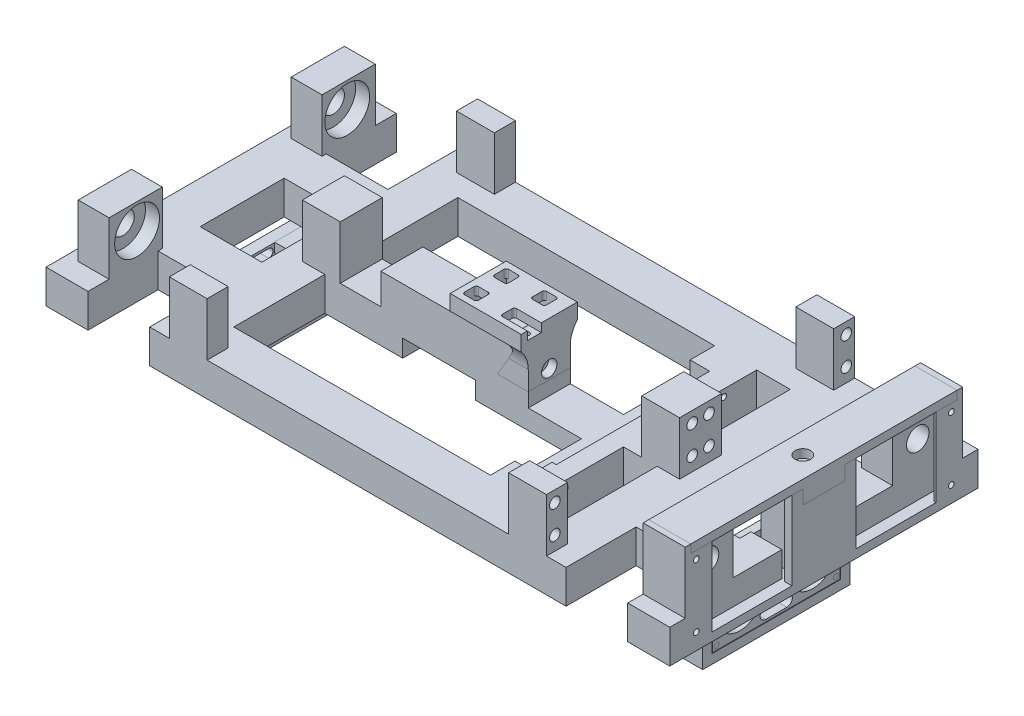
SolidWorks part; units mm, degrees
other "DogBody"
other "EspHolder"
other "HCSR04 Holder Front"
other "DisplayCover"
other "pin lu"
other "pin ru"
other "pin rd"
other "frontCover"
other "HCSR04 Holder Back"
other "pin rd2"
other "pin ru2"
other "pin lu2"
other "pin ld2"
other "frontCover2"
other "pin ld"
ref_plane "Front Plane" through (0, 0, 0) normal (0, 0, 1) x (1, 0, 0)
ref_plane "Top Plane" through (0, 0, 0) normal (0, 1, 0) x (1, 0, 0)
ref_plane "Right Plane" through (0, 0, 0) normal (1, 0, 0) x (0, 0, -1)
sketch "Sketch1" plane through (0, 0, 0) normal (0, 1, 0) x (1, 0, 0)
  line L0 (-96.3, -55) -> (-96.3, -7.5)
  line L1 (-111.3, -55) -> (-96.3, -55)
  line L2 (-111.3, -55) -> (-111.3, 55)
  line L3 (-111.3, 55) -> (-96.3, 55)
  line L4 (111.3, -55) -> (111.3, 55)
  line L5 (96.3, 55) -> (96.3, 7.5)
  line L6 (-74.3, -55) -> (-74.3, -7.5)
  line L7 (-59.3, -40) -> (-59.3, -7.5)
  line L8 (74.3, -55) -> (74.3, -7.5)
  line L9 (59.3, -40) -> (59.3, -7.5)
  line L10 (-111.3, 0) -> (111.3, 0) construction
  line L11 (-96.3, -7.5) -> (-74.3, -7.5)
  line L12 (-96.3, 7.5) -> (-74.3, 7.5)
  line L15 (-59.3, 40) -> (59.3, 40)
  line L16 (-74.3, 55) -> (74.3, 55)
  line L18 (96.3, 55) -> (111.3, 55)
  line L19 (96.3, -55) -> (111.3, -55)
  line L21 (-74.3, -55) -> (74.3, -55)
  line L22 (-59.3, -40) -> (59.3, -40)
  line L23 (-96.3, 7.5) -> (-96.3, 55)
  line L24 (-74.3, 7.5) -> (-74.3, 55)
  line L25 (-59.3, 7.5) -> (-59.3, 40)
  line L26 (59.3, 7.5) -> (59.3, 40)
  line L27 (74.3, 7.5) -> (74.3, 55)
  line L28 (96.3, -7.5) -> (96.3, -55)
  line L29 (-111.3, 7.5) -> (111.3, 7.5) construction
  line L30 (-111.3, -7.5) -> (111.3, -7.5) construction
  line L31 (74.3, -7.5) -> (96.3, -7.5)
  line L32 (74.3, 7.5) -> (96.3, 7.5)
  line L33 (-59.3, -7.5) -> (59.3, -7.5)
  line L34 (-59.3, 7.5) -> (59.3, 7.5)
  line L35 (-96.3, 55) -> (-74.3, 55) construction
  line L36 (74.3, 55) -> (96.3, 55) construction
  line L37 (74.3, -55) -> (96.3, -55) construction
  line L38 (-74.3, -55) -> (-96.3, -55) construction
  dimension "D1" = 55
  dimension "D2" = 110
  dimension "D3" = 15
  dimension "D4" = 22
  dimension "D5" = 15
  dimension "D6" = 15
  dimension "D7" = 22
  dimension "D8" = 15
  dimension "D11" = 80
  dimension "D12" = 40
  dimension "D13" = 222.6
  dimension "D14" = 111.3
  dimension "D9" = 7.5
  dimension "D10" = 7.5
extrude "Boss-Extrude1" add sketch "Sketch1" along normal blind 12
sketch "Sketch2" plane through (0, 12, 0) normal (0, 1, 0) x (1, 0, 0)
  line L0 (-74.3, 55) -> (-74.3, 7.5) construction
  line L1 (-67.3, 47.5) -> (-55.3, 47.5)
  line L2 (-67.3, 47.5) -> (-67.3, 55)
  line L3 (-67.3, 55) -> (-55.3, 55)
  line L4 (-55.3, 47.5) -> (-55.3, 55)
  line L5 (74.3, 55) -> (-74.3, 55) construction
  line L6 (-67.3, 52) -> (-55.3, 52) construction
  line L7 (-112.3144, 27.5) -> (114.0355, 27.5) construction
  line L8 (0, 0) -> (0, 64.2149) construction
  line L9 (-67.3, 3) -> (-55.3, 3) construction
  line L12 (-67.3, 7.5) -> (-55.3, 7.5)
  line L14 (0, 0) -> (-136.6898, 0) construction
  line L15 (-67.3, -52) -> (-55.3, -52) construction
  line L16 (-67.3, -55) -> (-55.3, -55)
  line L17 (-55.3, -47.5) -> (-55.3, -55)
  line L18 (-67.3, -47.5) -> (-55.3, -47.5)
  line L19 (-67.3, -47.5) -> (-67.3, -55)
  line L20 (-67.3, -3) -> (-55.3, -3) construction
  line L21 (-67.3, -7.5) -> (-55.3, -7.5)
  line L22 (-55.3, -7.5) -> (-55.3, 0)
  line L23 (-55.3, 0) -> (-55.3, 7.5)
  line L24 (-67.3, 7.5) -> (-67.3, 0)
  line L25 (-67.3, 0) -> (-67.3, -7.5)
  line L26 (67.3, -52) -> (55.3, -52) construction
  line L27 (67.3, -47.5) -> (67.3, -55)
  line L28 (67.3, -47.5) -> (55.3, -47.5)
  line L29 (55.3, -47.5) -> (55.3, -55)
  line L30 (67.3, -55) -> (55.3, -55)
  line L31 (67.3, -3) -> (55.3, -3) construction
  line L32 (67.3, 3) -> (55.3, 3) construction
  line L33 (67.3, 7.5) -> (67.3, 0)
  line L34 (67.3, 7.5) -> (55.3, 7.5)
  line L35 (55.3, 0) -> (55.3, 7.5)
  line L36 (55.3, -7.5) -> (55.3, 0)
  line L37 (67.3, -7.5) -> (55.3, -7.5)
  line L38 (67.3, 0) -> (67.3, -7.5)
  line L39 (67.3, 52) -> (55.3, 52) construction
  line L40 (67.3, 55) -> (55.3, 55)
  line L41 (55.3, 47.5) -> (55.3, 55)
  line L42 (67.3, 47.5) -> (55.3, 47.5)
  line L43 (67.3, 47.5) -> (67.3, 55)
  point P29 (-55.3, 0)
  point P32 (-67.3, 0)
  dimension "D1" = 7
  dimension "D2" = 7.5
  dimension "D3" = 12
  dimension "D5" = 24.5
extrude "Boss-Extrude2" add sketch "Sketch2" along normal blind 19
sketch "Sketch3" plane through (-67.3, 0, 0) normal (-1, 0, 0) x (0, 0, 1)
  line L0 (-27.5, -10.7851) -> (-27.5, 36.9377) construction
  line L1 (-47.5, 31) -> (-47.5, 12) construction
  line L2 (-55, 12) -> (55, 12) construction
  line L3 (0, 0) -> (0, 40.8102) construction
  line L4 (-55, 0) -> (55, 0) construction
  circle A0 centre (-52, 17) radius 1.9
  circle A1 centre (-52, 27) radius 1.9
  circle A2 centre (-3, 17) radius 1.9
  circle A3 centre (-3, 27) radius 1.9
  circle A4 centre (3, 27) radius 1.9
  circle A5 centre (3, 17) radius 1.9
  circle A6 centre (52, 17) radius 1.9
  circle A7 centre (52, 27) radius 1.9
  dimension "D3" = 3.8
  dimension "D4" = 3.8
  dimension "D1" = 4.5
  dimension "D2" = 4.5
  dimension "D5" = 10
  dimension "D6" = 5
  dimension "D7" = 24.5
extrude "Cut-Extrude1" cut sketch "Sketch3" against normal through all
sketch "Sketch4" plane through (96.3, 0, 0) normal (-1, 0, 0) x (0, 0, 1)
  line L0 (47.5, 31) -> (47.5, 12) construction
  line L1 (-55, 12) -> (55, 12) construction
  line L2 (-1000, 0) -> (49000, 0) construction
  line L3 (0, -1000) -> (0, 49000) construction
  line L5 (-47.5, 12) -> (-28.5, 12)
  line L6 (-47.5, 12) -> (-47.5, 31)
  line L7 (-47.5, 31) -> (-28.5, 31)
  line L8 (-28.5, 12) -> (-28.5, 31)
  line L9 (47.5, 12) -> (28.5, 12)
  line L10 (47.5, 12) -> (47.5, 31)
  line L11 (47.5, 31) -> (28.5, 31)
  line L12 (28.5, 12) -> (28.5, 31)
  circle A0 centre (37.5, 22) radius 8
  circle A1 centre (-37.5, 22) radius 8
  dimension "D1" = 16
  dimension "D2" = 10
  dimension "D3" = 10
  dimension "D4" = 19
  dimension "D5" = 19
  dimension "D6" = 19
  dimension "D7" = 19
extrude "Boss-Extrude3" add sketch "Sketch4" against normal blind 5 separate body
sketch "Sketch6" plane through (101.3, 0, 0) normal (1, 0, 0) x (0, 0, -1)
  line L6 (-47.5, 12) -> (-28.5, 12)
  line L7 (-47.5, 12) -> (-47.5, 31)
  line L8 (-47.5, 31) -> (-28.5, 31)
  line L9 (-28.5, 12) -> (-28.5, 31)
  line L10 (47.5, 12) -> (28.5, 12)
  line L11 (47.5, 12) -> (47.5, 31)
  line L12 (47.5, 31) -> (28.5, 31)
  line L13 (28.5, 12) -> (28.5, 31)
  circle A0 centre (-37.5, 22) radius 4
  circle A1 centre (37.5, 22) radius 4
  dimension "D1" = 8
  dimension "D2" = 8
extrude "Boss-Extrude4" add sketch "Sketch6" along normal blind 6
mirror "Mirror1" about plane through (0, 0, 0) normal (1, 0, 0) of bodies 107 106
sketch "Sketch7" plane through (0, 0, 0) normal (0, 1, 0) x (1, 0, 0)
  line L0 (-96.3, 28.5) -> (-96.3, 47.5) construction
  line L1 (-96.3, 30) -> (-74.3, 30)
  line L2 (-96.3, 30) -> (-96.3, 15)
  line L4 (-74.3, 30) -> (-74.3, 15)
  line L5 (-67.3, 47.5) -> (-55.3, 47.5) construction
  line L7 (-96.3, 15) -> (-74.3, 15)
  line L9 (-1000, 0) -> (49000, 0) construction
  line L10 (0, -1000) -> (0, 49000) construction
  line L11 (96.3, 30) -> (96.3, 15)
  line L12 (96.3, 15) -> (74.3, 15)
  line L13 (74.3, 30) -> (74.3, 15)
  line L14 (96.3, 30) -> (74.3, 30)
  line L15 (96.3, -30) -> (74.3, -30)
  line L16 (74.3, -30) -> (74.3, -15)
  line L17 (96.3, -15) -> (74.3, -15)
  line L18 (96.3, -30) -> (96.3, -15)
  line L19 (-96.3, -30) -> (-96.3, -15)
  line L20 (-96.3, -15) -> (-74.3, -15)
  line L21 (-74.3, -30) -> (-74.3, -15)
  line L22 (-96.3, -30) -> (-74.3, -30)
  dimension "D1" = 17.5
  dimension "D2" = 15
  dimension "D3" = 22
extrude "Boss-Extrude5" add sketch "Sketch7" along normal blind 12
sketch "Sketch8" plane through (0, 12, 0) normal (0, 1, 0) x (1, 0, 0)
  line L1 (-96.3, 15) -> (-74.3, 15)
  line L2 (-96.3, 15) -> (-96.3, -15)
  line L3 (-96.3, -15) -> (-74.3, -15)
  line L4 (-74.3, 15) -> (-74.3, -15)
  line L5 (74.3, -15) -> (96.3, -15)
  line L6 (74.3, -15) -> (74.3, 15)
  line L7 (74.3, 15) -> (96.3, 15)
  line L8 (96.3, -15) -> (96.3, 15)
extrude "Cut-Extrude2" cut sketch "Sketch8" against normal through all
sketch "Sketch9" plane through (111.3, 0, 0) normal (1, 0, 0) x (0, 0, -1)
  line L1 (-47.5, 31) -> (-7.5, 31)
  line L2 (-47.5, 31) -> (-47.5, 3)
  line L3 (-47.5, 3) -> (-7.5, 3)
  line L4 (-7.5, 31) -> (-7.5, 3)
  line L5 (0, -1000) -> (0, 49000) construction
  line L6 (-55, 0) -> (55, 0) construction
  line L7 (47.5, 3) -> (7.5, 3)
  line L8 (7.5, 31) -> (7.5, 3)
  line L9 (47.5, 31) -> (7.5, 31)
  line L10 (47.5, 31) -> (47.5, 3)
  point P10 (0, 0)
  dimension "D1" = 28
  dimension "D2" = 40
extrude "Cut-Extrude3" cut sketch "Sketch9" against normal blind 4
sketch "Sketch10" plane through (107.3, 0, 0) normal (1, 0, 0) x (0, 0, -1)
  line L1 (-28.5, 31) -> (-47.5, 31) construction
  line L2 (-47.5, 31) -> (-47.5, 12) construction
  line L3 (-47.5, 12) -> (-47.5, 3) construction
  line L4 (0, -1000) -> (0, 49000) construction
  circle A0 centre (-45.5, 28.25) radius 1
  circle A1 centre (-45.5, 5.75) radius 1
  circle A2 centre (45.5, 5.75) radius 1
  circle A3 centre (45.5, 28.25) radius 1
  dimension "D1" = 2
  dimension "D2" = 2
  dimension "D3" = 22.5
  dimension "D4" = 2.75
  dimension "D5" = 2
  dimension "D6" = 2
sketch "Sketch11" plane through (107.3, 0, 0) normal (1, 0, 0) x (0, 0, -1)
  line L0 (-7.5, 12) -> (-28.5, 12) construction
  line L1 (-7.5, 3) -> (-11, 3)
  line L2 (-7.5, 3) -> (-7.5, 12)
  line L3 (-7.5, 12) -> (-11, 12)
  line L4 (-11, 3) -> (-11, 12)
  line L5 (7.5, 12) -> (28.5, 12) construction
  line L6 (7.5, 3) -> (11, 3)
  line L7 (7.5, 3) -> (7.5, 12)
  line L8 (7.5, 12) -> (11, 12)
  line L9 (11, 3) -> (11, 12)
  dimension "D1" = 3.5
  dimension "D2" = 3.5
extrude "Cut-Extrude5" cut sketch "Sketch11" against normal up to next
sketch "Sketch12" plane through (0, 3, 0) normal (0, 1, 0) x (1, 0, 0)
  line L0 (108.6, -11.4) -> (111.3, -11.4)
  line L1 (111.3, -47.5) -> (108.6, -47.5)
  line L2 (111.3, -47.5) -> (111.3, -42.5)
  line L3 (110.6, -42.5) -> (108.6, -42.5)
  line L4 (108.6, -47.5) -> (108.6, -42.5)
  line L6 (111.3, -42.5) -> (111.3, -40)
  line L7 (111.3, -40) -> (110.6, -40)
  line L8 (110.6, -42.5) -> (110.6, -40)
  line L9 (111.3, -7.5) -> (110.6, -7.5)
  line L10 (111.3, -7.5) -> (111.3, -11.4)
  line L12 (110.6, -7.5) -> (110.6, -10.4)
  line L15 (110.6, -10.4) -> (108.6, -10.4)
  line L16 (108.6, -11.4) -> (108.6, -10.4)
  line L18 (-1000, 0) -> (49000, 0) construction
  line L20 (111.3, 47.5) -> (108.6, 47.5)
  line L21 (108.6, 47.5) -> (108.6, 42.5)
  line L22 (110.6, 42.5) -> (108.6, 42.5)
  line L23 (110.6, 42.5) -> (110.6, 40)
  line L24 (111.3, 40) -> (110.6, 40)
  line L25 (111.3, 42.5) -> (111.3, 40)
  line L26 (111.3, 47.5) -> (111.3, 42.5)
  line L27 (108.6, 11.4) -> (108.6, 10.4)
  line L28 (110.6, 10.4) -> (108.6, 10.4)
  line L29 (110.6, 7.5) -> (110.6, 10.4)
  line L30 (111.3, 7.5) -> (110.6, 7.5)
  line L31 (111.3, 7.5) -> (111.3, 11.4)
  line L32 (108.6, 11.4) -> (111.3, 11.4)
  dimension "D1" = 2.7
  dimension "D2" = 5
  dimension "D3" = 2.5
  dimension "D4" = 0.7
  dimension "D5" = 3.9
  dimension "D6" = 0.7
  dimension "D7" = 5
  dimension "D8" = 1
  dimension "D9" = 2
extrude "Boss-Extrude6" add sketch "Sketch12" along normal up to surface (28 mm away) up to face at (101.8, 31, 38)
extrude "Cut-Extrude7" cut sketch "Sketch10" against normal blind 3 and the other way through all
sketch "Sketch13" plane through (0, 12, 0) normal (0, 1, 0) x (1, 0, 0)
  line L1 (111.3, 7.5) -> (96.3, 7.5)
  line L2 (111.3, 7.5) -> (111.3, -7.5)
  line L3 (111.3, -7.5) -> (96.3, -7.5)
  line L4 (96.3, 7.5) -> (96.3, -7.5)
extrude "Boss-Extrude7" add sketch "Sketch13" along normal blind 14
sketch "Sketch14" plane through (0, 0, 0) normal (0, 1, 0) x (1, 0, 0)
  line L0 (-59.3, -40) -> (59.3, -40) construction
  line L1 (-7.5, -40) -> (7.5, -40)
  line L2 (-7.5, -40) -> (-7.5, -7.5)
  line L3 (-7.5, 40) -> (7.5, 40)
  line L4 (7.5, -40) -> (7.5, -7.5)
  line L5 (59.3, 40) -> (-59.3, 40) construction
  line L6 (55.3, -7.5) -> (-55.3, -7.5) construction
  line L7 (-55.3, 7.5) -> (55.3, 7.5) construction
  line L8 (7.5, -7.5) -> (-7.5, -7.5)
  line L9 (-7.5, 7.5) -> (7.5, 7.5)
  line L10 (7.5, 7.5) -> (7.5, 40)
  line L11 (-7.5, 7.5) -> (-7.5, 40)
  dimension "D1" = 15
  dimension "D2" = 7.5
extrude "Boss-Extrude8" add sketch "Sketch14" along normal up to surface (12 mm away) up to face at (0, 12, 0)
sketch "Sketch15" plane through (0, 12, 0) normal (0, 1, 0) x (1, 0, 0)
  line L1 (13.3, -31.25) -> (39.3, -31.25)
  line L2 (13.3, -31.25) -> (13.3, 31.25)
  line L4 (39.3, -31.25) -> (39.3, 31.25)
  line L5 (67.3, 47.5) -> (67.3, 55) construction
  line L8 (13.3, 31.25) -> (39.3, 31.25)
  line L9 (-39.3, 14) -> (8.7, 14)
  line L10 (-39.3, 14) -> (-39.3, -14)
  line L11 (-39.3, -14) -> (8.7, -14)
  line L12 (8.7, 14) -> (8.7, -14)
  line L13 (13.3, 27.75) -> (39.3, 27.75) construction
  line L14 (13.3, -27.75) -> (39.3, -27.75) construction
  line L15 (-67.3, 55) -> (-67.3, 47.5) construction
  line L16 (-39.3, -998.765) -> (-39.3, 49001.235) construction
  line L17 (39.3, -1009.0627) -> (39.3, 48990.9373) construction
  point P17 (-67.3, 51.25)
  dimension "D1" = 26
  dimension "D2" = 28
  dimension "D3" = 48
  dimension "D4" = 28
  dimension "D5" = 31.25
  dimension "D6" = 62.5
  dimension "D7" = 55.5
  dimension "D8" = 3.5
  dimension "D9" = 28
  dimension "D10" = 14
  dimension "D11" = 4.6
sketch "Sketch16" plane through (0, 12, 0) normal (0, 1, 0) x (1, 0, 0)
  line L1 (-7.5, 40) -> (7.5, 40)
  line L2 (-7.5, 40) -> (-7.5, 7.5)
  line L3 (-7.5, 7.5) -> (7.5, 7.5)
  line L4 (7.5, 40) -> (7.5, 7.5)
  line L5 (-7.5, -7.5) -> (7.5, -7.5)
  line L6 (-7.5, -7.5) -> (-7.5, -40)
  line L7 (-7.5, -40) -> (7.5, -40)
  line L8 (7.5, -7.5) -> (7.5, -40)
extrude "Cut-Extrude8" cut sketch "Sketch16" against normal through all
sketch "Sketch17" plane through (0, 0, 0) normal (0, 1, 0) x (1, 0, 0)
  line L0 (59.3, 40) -> (-59.3, 40) construction
  line L1 (32.3, 40) -> (47.3, 40)
  line L2 (32.3, 40) -> (32.3, 7.5)
  line L3 (32.3, 7.5) -> (47.3, 7.5)
  line L4 (47.3, 40) -> (47.3, 7.5)
  line L5 (-55.3, 7.5) -> (55.3, 7.5) construction
  line L6 (55.3, -7.5) -> (-55.3, -7.5) construction
  line L7 (32.3, -7.5) -> (47.3, -7.5)
  line L8 (32.3, -7.5) -> (32.3, -40)
  line L9 (32.3, -40) -> (47.3, -40)
  line L10 (47.3, -7.5) -> (47.3, -40)
  line L11 (-59.3, -40) -> (59.3, -40) construction
  line L12 (39.3, -201009.0627) -> (39.3, 248990.9373) construction
  dimension "D1" = 15
  dimension "D2" = 15
  dimension "D3" = 7
  dimension "D4" = 7
extrude "Boss-Extrude9" add sketch "Sketch17" along normal up to surface (12 mm away) up to face at (-85.3, 12, 0)
extrude "Cut-Extrude9" cut sketch "Sketch15" against normal blind 5 contours L8 L2 L1 L4 region at (26.3, 12, 0)
sketch "Sketch18" plane through (39.3, 0, 0) normal (-1, 0, 0) x (0, 0, 1)
  line L0 (31.25, 7) -> (-31.25, 7) construction
  line L1 (-31.25, 12) -> (-31.25, 7) construction
  line L2 (31.25, 12) -> (31.25, 7) construction
  circle A0 centre (28.25, 9.5) radius 1
  circle A1 centre (-28.25, 9.5) radius 1
  dimension "D1" = 2
  dimension "D2" = 2
  dimension "D3" = 2.5
  dimension "D4" = 2.5
  dimension "D5" = 3
  dimension "D6" = 3
extrude "Cut-Extrude10" cut sketch "Sketch18" against normal up to next
sketch "Sketch19" plane through (39.3, 0, 0) normal (-1, 0, 0) x (0, 0, 1)
  line L0 (-31.25, 7) -> (-7.5, 7) construction
  line L1 (-25, 7) -> (25, 7)
  line L2 (-25, 7) -> (-25, 14)
  line L3 (-25, 14) -> (25, 14)
  line L4 (25, 7) -> (25, 14)
  dimension "D1" = 7
  dimension "D2" = 50
  dimension "D3" = 25
extrude "Cut-Extrude11" cut sketch "Sketch19" against normal blind 1.5
sketch "Sketch21" plane through (0, 0, 7.5) normal (0, 0, 1) x (1, 0, 0)
  line L0 (-39.3, 12) -> (8.7, 12) construction
  line L1 (-39.3, 12) -> (2.3491, 12)
  line L2 (-39.3, 12) -> (-39.3, 23)
  line L3 (-39.3, 23) -> (8.7, 23)
  line L5 (13.3, 12) -> (-55.3, 12) construction
  line L6 (8.7, 23) -> (2.3491, 12)
  dimension "D1" = 60
  dimension "D2" = 11
  dimension "D3" = 48
  dimension "D4" = 39.3
extrude "Boss-Extrude10" add sketch "Sketch21" against normal up to surface (15 mm away) up to face at (-27.26, 12.4, -7.5)
sketch "Sketch22" plane through (0, 0, 7.5) normal (0, 0, 1) x (1, 0, 0)
  line L0 (2.3491, 12) -> (13.3, 12)
  line L1 (13.3, 12) -> (13.3, 23)
  line L2 (8.7, 23) -> (2.3491, 12)
  line L3 (8.7, 23) -> (13.3, 23)
extrude "Boss-Extrude11" add sketch "Sketch22" against normal up to surface (15 mm away) separate body up to face at (-24.2965, 13.8571, -7.5)
sketch "Sketch25" plane through (13.3, 0, 0) normal (1, 0, 0) x (0, 0, -1)
  line L0 (-7.5, 23) -> (7.5, 23)
  line L2 (-7.5, 31) -> (7.5, 31) construction
  line L3 (10, 31) -> (-10, 31)
  line L6 (10, 31) -> (10, 25.5)
  line L7 (7.5, 23) -> (10, 25.5)
  line L8 (-10, 25.5) -> (-10, 31)
  line L9 (-7.5, 23) -> (-10, 25.5)
  dimension "D1" = 20
  dimension "D2" = 10
  dimension "D3" = 5.5
  dimension "D4" = 5.5
extrude "Boss-Extrude12" add sketch "Sketch25" against normal blind 4.6
sketch "Sketch28" plane through (8.7, 0, 0) normal (-1, 0, 0) x (0, 0, 1)
  line L0 (-10, 31) -> (10, 31)
  line L1 (10, 31) -> (10, 25.5)
  line L2 (10, 31) -> (10, 25.5) construction
  line L3 (10, 25.5) -> (7.85, 25.5)
  line L4 (7.85, 25.5) -> (7.85, 28)
  line L5 (7.85, 28) -> (-7.85, 28)
  line L6 (-7.85, 28) -> (-7.85, 25.5)
  line L7 (-7.85, 25.5) -> (-10, 25.5)
  line L8 (-10, 25.5) -> (-10, 31) construction
  line L9 (-10, 25.5) -> (-10, 31)
  dimension "D1" = 15.7
  dimension "D2" = 7.85
  dimension "D3" = 3
  dimension "D4" = 2.5
  dimension "D5" = 2.5
extrude "Boss-Extrude13" add sketch "Sketch28" along normal blind 18.6
sketch "Sketch29" plane through (-9.9, 0, 0) normal (-1, 0, 0) x (0, 0, 1)
  line L1 (-10, 31) -> (10, 31)
  line L2 (-10, 31) -> (-10, 25.5)
  line L3 (-10, 25.5) -> (10, 25.5)
  line L4 (10, 31) -> (10, 25.5)
extrude "Boss-Extrude14" add sketch "Sketch29" along normal blind 2.15
sketch "Sketch31" plane through (0, 28, 0) normal (0, -1, 0) x (1, 0, 0)
  line L0 (13.3, 31.25) -> (13.3, -31.25) construction
  line L1 (7.9, 7.85) -> (4.5, 7.85)
  line L2 (8.7, 7.05) -> (8.7, 3.65) construction
  line L3 (7.9, 2.85) -> (4.5, 2.85)
  line L4 (3.7, 7.05) -> (3.7, 3.65)
  line L5 (7.9, 7.85) -> (13.3, 7.85)
  line L6 (7.9, 7.85) -> (7.9, 2.85)
  line L7 (7.9, 2.85) -> (13.3, 2.85)
  line L8 (-9.9, 7.05) -> (-9.9, 3.65)
  line L9 (-5.7, 7.85) -> (-9.1, 7.85)
  line L10 (-4.9, 7.05) -> (-4.9, 3.65)
  line L11 (-5.7, 2.85) -> (-9.1, 2.85)
  line L12 (-5.7, -7.85) -> (-9.1, -7.85)
  line L13 (-4.9, -3.65) -> (-4.9, -7.05)
  line L14 (-5.7, -2.85) -> (-9.1, -2.85)
  line L15 (-9.9, -3.65) -> (-9.9, -7.05)
  line L16 (7.9, -2.85) -> (4.5, -2.85)
  line L17 (7.9, -7.85) -> (4.5, -7.85)
  line L18 (8.7, -3.65) -> (8.7, -7.05)
  line L19 (3.7, -3.65) -> (3.7, -7.05)
  line L20 (13.3, 7.85) -> (13.3, 2.85)
  arc A3 (4.5, 2.85) -> (3.7, 3.65) centre (4.5, 3.65) cw
  arc A4 (8.7, 3.65) -> (7.9, 2.85) centre (7.9, 3.65) cw construction
  arc A5 (7.9, 7.85) -> (8.7, 7.05) centre (7.9, 7.05) cw construction
  arc A6 (4.5, 7.85) -> (3.7, 7.05) centre (4.5, 7.05) ccw
  arc A7 (-5.7, 7.85) -> (-4.9, 7.05) centre (-5.7, 7.05) cw
  arc A8 (-9.1, 2.85) -> (-9.9, 3.65) centre (-9.1, 3.65) cw
  arc A9 (-9.1, 7.85) -> (-9.9, 7.05) centre (-9.1, 7.05) ccw
  arc A10 (-4.9, 3.65) -> (-5.7, 2.85) centre (-5.7, 3.65) cw
  arc A11 (-4.9, -7.05) -> (-5.7, -7.85) centre (-5.7, -7.05) cw
  arc A12 (-9.1, -7.85) -> (-9.9, -7.05) centre (-9.1, -7.05) cw
  arc A13 (-9.1, -2.85) -> (-9.9, -3.65) centre (-9.1, -3.65) ccw
  arc A14 (-5.7, -2.85) -> (-4.9, -3.65) centre (-5.7, -3.65) cw
  arc A15 (7.9, -2.85) -> (8.7, -3.65) centre (7.9, -3.65) cw
  arc A16 (4.5, -2.85) -> (3.7, -3.65) centre (4.5, -3.65) ccw
  arc A17 (4.5, -7.85) -> (3.7, -7.05) centre (4.5, -7.05) cw
  arc A18 (8.7, -7.05) -> (7.9, -7.85) centre (7.9, -7.05) cw
  point P21 (3.7, 2.85)
  point P26 (8.7, 7.85)
  point P29 (3.7, 7.85)
  line M4 (8.7, -7.85) -> (8.7, 7.85)
  line M5 (8.7, 7.85) -> (-9.9, 7.85)
  line M6 (-9.9, 7.85) -> (-9.9, -7.85)
  line M7 (-9.9, -7.85) -> (8.7, -7.85)
  dimension "D3" = 8.6
  dimension "D4" = 2.85
  dimension "D5" = 5.7
  dimension "D12" = 0.8
  dimension "D1" = 5
  dimension "D2" = 5
  dimension "D6" = 3.7
  dimension "D7" = 2.85
  dimension "D8" = 4.9
extrude "Cut-Extrude12" cut sketch "Sketch31" against normal through all contours A10 L10 A7 A9 A8 L11 M5 M6 | A14 L14 A13 A12 A11 L13 M6 M7 | A18 A15 L16 A16 L19 A17 M4 M7 | A6 L4 A3 L3 L6 M5 | L20 L5 L7 M4 | L6 L7 M4 M5 region at (5.8255, 28, 5.35) region at (8.3, 28, 5.35) region at (11, 28, 5.35) region at (-7.4, 28, 5.35) region at (6.2, 28, -5.35) region at (-7.4, 28, -5.35)
fillet "Fillet1" radius 10 2 edges at (11, 23, -7.5) (11, 23, 7.5)
sketch "Sketch32" plane through (13.3, 0, 0) normal (1, 0, 0) x (0, 0, -1)
  line L0 (-31.25, 12) -> (31.25, 12) construction
  circle A1 centre (0, 15.5) radius 2.75
  dimension "D1" = 5.5
  dimension "D2" = 3.5
extrude "Cut-Extrude13" cut sketch "Sketch32" against normal blind 3
sketch "Sketch33" plane through (10.3, 0, 0) normal (1, 0, 0) x (0, 0, -1)
  circle A0 centre (0, 15.5) radius 1.425
  dimension "D1" = 2.85
extrude "Cut-Extrude14" cut sketch "Sketch33" against normal blind 20
sketch "Sketch34" plane through (0, 28, 0) normal (0, 1, 0) x (1, 0, 0)
  line L0 (13.3, -7.85) -> (8.7, -7.85) construction
  line L2 (13.3, -31.25) -> (13.3, 31.25) construction
  circle A0 centre (11, -5.85) radius 1
  dimension "D1" = 2
  dimension "D2" = 2
  dimension "D3" = 2.3
extrude "Cut-Extrude15" cut sketch "Sketch34" against normal through all
sketch "Sketch35" plane through (0, 26, 0) normal (0, 1, 0) x (1, 0, 0)
  line L6 (111.3, -7.5) -> (111.3, 7.5)
  line L7 (111.3, 7.5) -> (110.6, 7.5)
  line L8 (110.6, 7.5) -> (96.3, 7.5)
  line L9 (96.3, 7.5) -> (96.3, -7.5)
  line L10 (96.3, -7.5) -> (110.6, -7.5)
  line L11 (110.6, -7.5) -> (111.3, -7.5)
  line L12 (111.3, -7.5) -> (111.3, 7.5)
  line L13 (111.3, 7.5) -> (110.6, 7.5)
  line L14 (110.6, 7.5) -> (96.3, 7.5)
  line L15 (96.3, 7.5) -> (96.3, -7.5)
  line L16 (96.3, -7.5) -> (110.6, -7.5)
  line L17 (110.6, -7.5) -> (111.3, -7.5)
  dimension "D1" = 0
extrude "Boss-Extrude15" add sketch "Sketch35" along normal up to surface (5 mm away) separate body up to face at (110.1667, 31, 9.7667)
sketch "Sketch36" plane through (0, 31, 0) normal (0, 1, 0) x (1, 0, 0)
  line L0 (96.3, 7.5) -> (96.3, 47.5)
  line L1 (96.3, 47.5) -> (111.3, 47.5)
  line L2 (111.3, 47.5) -> (111.3, 7.5)
  line L3 (96.3, -7.5) -> (96.3, -47.5)
  line L4 (96.3, -7.5) -> (111.3, -7.5)
  line L5 (111.3, -7.5) -> (111.3, 7.5)
  line L6 (111.3, 7.5) -> (96.3, 7.5)
  line L7 (96.3, 7.5) -> (96.3, -7.5)
  line L9 (111.3, -7.5) -> (111.3, 7.5)
  line L11 (96.3, 7.5) -> (96.3, -7.5)
  line L12 (96.3, -47.5) -> (111.3, -47.5)
  line L13 (111.3, -47.5) -> (111.3, -7.5)
  dimension "D1" = 0
extrude "Boss-Extrude16" add sketch "Sketch36" along normal blind 3
sketch "Sketch37" plane through (0, 34, 0) normal (0, 1, 0) x (1, 0, 0)
  line L1 (96.3, 47.5) -> (96.3, -47.5) construction
  circle A0 centre (103.8, 0) radius 2.75
  point P2 (0, 0)
  dimension "D2" = 5.5
  dimension "D1" = 7.5
extrude "Cut-Extrude16" cut sketch "Sketch37" against normal blind 3
sketch "Sketch38" plane through (0, 31, 0) normal (0, 1, 0) x (1, 0, 0)
  circle A0 centre (103.8, 0) radius 1.4
  dimension "D1" = 2.8
extrude "Cut-Extrude17" cut sketch "Sketch38" against normal blind 20
sketch "Sketch39" plane through (0, 31, 0) normal (0, 1, 0) x (1, 0, 0)
  line L0 (107.3, -47.5) -> (96.3, -47.5) construction
  line L1 (-1000, 0) -> (49000, 0) construction
  line L2 (96.3, -47.5) -> (96.3, -28.5) construction
  circle A0 centre (101.8, -45.5) radius 1.5
  circle A1 centre (101.8, 45.5) radius 1.5
  dimension "D2" = 3
  dimension "D1" = 2
  dimension "D3" = 5.5
extrude "Cut-Extrude18" cut sketch "Sketch39" against normal blind 3.5
extrude "Boss-Extrude17" add sketch "Sketch39<2>" against normal blind 3.5
sketch "Sketch39<2>" plane through (0, 31, 0) normal (0, 1, 0) x (1, 0, 0) same geometry as "Sketch39"
sketch "Sketch41" plane through (0, 0, 0) normal (0, -1, 0) x (1, 0, 0)
  line L0 (80.3, 21) -> (90.3, 21) construction
  line L1 (80.3, -22.75) -> (90.3, -22.75) construction
  line L2 (80.3, -22.75) -> (80.3, 22.75) construction
  line L3 (80.3, 22.75) -> (90.3, 22.75) construction
  line L4 (90.3, -22.75) -> (90.3, 22.75) construction
  line L5 (80.3, -21) -> (90.3, -21) construction
  line L6 (96.3, -15) -> (96.3, 15) construction
  line L8 (85.3, 22.75) -> (85.3, -22.75) construction
  line L24 (85.3, -22.75) -> (82.3, -22.75)
  line L25 (85.3, -22.75) -> (85.3, 22.75)
  line L26 (85.3, 22.75) -> (82.3, 22.75)
  line L27 (82.3, -22.75) -> (82.3, 22.75)
  line L28 (82.3, 22.75) -> (85.3, 22.75)
  line L29 (82.3, 22.75) -> (82.3, 26.25)
  line L30 (82.3, 26.25) -> (85.3, 26.25)
  line L31 (85.3, 22.75) -> (85.3, 26.25)
  line L32 (82.3, -22.75) -> (85.3, -22.75)
  line L33 (82.3, -22.75) -> (82.3, -26.25)
  line L34 (82.3, -26.25) -> (85.3, -26.25)
  line L35 (85.3, -22.75) -> (85.3, -26.25)
  line M29 (74.3, 15) -> (96.3, 15)
  line M31 (96.3, -15) -> (74.3, -15)
  dimension "D1" = 45.5
  dimension "D2" = 22.75
  dimension "D3" = 42
  dimension "D4" = 21
  dimension "D5" = 10
  dimension "D6" = 6
  dimension "D7" = 3.5
  dimension "D8" = 3.5
  dimension "D9" = 3
extrude "Boss-Extrude18" add sketch "Sketch41" along normal blind 24 separate body contours L26 L31 L30 L29 | L27 L25 L26 M29 | L27 L25 M31 M29 | L27 L24 L25 M31 | L35 L24 L33 L34 region at (83.8, 0, -24.5) region at (83.8, 0, -18.875) region at (83.8, 0, 0) region at (83.8, 0, 18.875) region at (83.8, 0, 24.5)
sketch "Sketch42" plane through (85.3, 0, 0) normal (1, 0, 0) x (0, 0, -1)
  line L1 (-26.25, 0) -> (26.25, 0)
  line L2 (-26.25, 0) -> (-26.25, -24)
  line L3 (-26.25, -24) -> (26.25, -24)
  line L4 (26.25, 0) -> (26.25, -24)
  line L5 (-22.95, 0) -> (22.95, 0)
  line L6 (-22.95, 0) -> (-22.95, -20.7)
  line L7 (-22.95, -20.7) -> (22.95, -20.7)
  line L8 (22.95, 0) -> (22.95, -20.7)
  line L9 (-5.5, -5.0608) -> (5.5, -5.0608) construction
  line L10 (-5.5, -5.0608) -> (-5.5, 3.3558) construction
  line L11 (-5.5, 3.3558) -> (5.5, 3.3558) construction
  line L12 (5.5, -5.0608) -> (5.5, 3.3558) construction
  line L13 (-5.5, -3.3) -> (-19.95, -3.3)
  line L14 (-5.5, -3.3) -> (-5.5, 0)
  line L15 (-5.5, 0) -> (-19.95, 0)
  line L16 (-19.95, -3.3) -> (-19.95, 0)
  line L17 (5.5, -3.3) -> (19.95, -3.3)
  line L18 (5.5, -3.3) -> (5.5, 0)
  line L19 (5.5, 0) -> (19.95, 0)
  line L20 (19.95, -3.3) -> (19.95, 0)
  line M8 (26.25, 0) -> (-26.25, 0)
  line M9 (-26.25, 0) -> (-26.25, -24)
  line M10 (-26.25, -24) -> (26.25, -24)
  line M11 (26.25, -24) -> (26.25, 0)
  dimension "D1" = 3.3
  dimension "D2" = 3.3
  dimension "D3" = 3.3
  dimension "D4" = 11
  dimension "D5" = 5.5
  dimension "D6" = 3.3
  dimension "D7" = 3.3
  dimension "D8" = 3
  dimension "D9" = 3
extrude "Boss-Extrude19" add sketch "Sketch42" along normal blind 9 contours L8 L7 L6 M8 M9 M10 M11 region at (85.3, -0.5773, 24.6)
sketch "Sketch43" plane through (85.3, 0, 0) normal (1, 0, 0) x (0, 0, -1)
  line L0 (-55, 0) -> (55, 0) construction
  line L1 (-21.25, -1.5) -> (21.25, -1.5) construction
  line L2 (-21.25, -1.5) -> (-21.25, -19) construction
  line L3 (-21.25, -19) -> (21.25, -19) construction
  line L4 (21.25, -1.5) -> (21.25, -19) construction
  line L5 (-22.95, 0) -> (-22.95, -20.7) construction
  line L7 (22.95, 0) -> (22.95, -20.7) construction
  line L9 (-22.95, -20.7) -> (22.95, -20.7) construction
  circle A1 centre (-21.25, -1.5) radius 0.9
  circle A2 centre (-21.25, -19) radius 0.9
  circle A3 centre (21.25, -1.5) radius 0.9
  circle A4 centre (21.25, -19) radius 0.9
  point P19 (0, 0)
  point P20 (0, 0)
  dimension "D5" = 1.8
  dimension "D6" = 1.8
  dimension "D7" = 1.8
  dimension "D8" = 1.8
  dimension "D1" = 1.5
  dimension "D2" = 1.7
  dimension "D3" = 1.7
  dimension "D4" = 1.7
extrude "Cut-Extrude19" cut sketch "Sketch43" against normal blind 2
sketch "Sketch44" plane through (82.3, 0, 0) normal (-1, 0, 0) x (0, 0, 1)
  line L0 (-26.25, 0) -> (26.25, 0) construction
  line L1 (-26.25, 0) -> (-18.75, 0)
  line L2 (-26.25, 0) -> (-26.25, -5)
  line L3 (-26.25, -5) -> (-18.75, -5)
  line L4 (-18.75, 0) -> (-18.75, -5)
  line L6 (26.25, 0) -> (18.75, 0)
  line L7 (26.25, 0) -> (26.25, -5)
  line L8 (26.25, -5) -> (18.75, -5)
  line L9 (18.75, 0) -> (18.75, -5)
  dimension "D1" = 7.5
  dimension "D2" = 7.5
  dimension "D3" = 5
  dimension "D4" = 5
  dimension "D5" = 18.75
  dimension "D6" = 18.75
extrude "Boss-Extrude20" add sketch "Sketch44" along normal blind 7.5
sketch "Sketch45" plane through (0, -5, 0) normal (0, -1, 0) x (1, 0, 0)
  line L0 (74.8, -26.25) -> (74.8, -18.75) construction
  line L1 (74.8, -26.25) -> (82.3, -26.25) construction
  line L2 (74.8, 18.75) -> (74.8, 26.25) construction
  line L3 (74.8, 26.25) -> (82.3, 26.25) construction
  circle A0 centre (78.55, 22.5) radius 2.75
  circle A1 centre (78.55, -22.5) radius 2.75
  dimension "D3" = 5.5
  dimension "D4" = 5.5
  dimension "D1" = 3.75
  dimension "D2" = 3.75
  dimension "D5" = 3.75
  dimension "D6" = 3.75
extrude "Cut-Extrude20" cut sketch "Sketch45" against normal blind 3
mirror "Mirror4" about plane through (0, 0, 0) normal (1, 0, 0) of bodies 163
sketch "Sketch47" plane through (0, -2, 0) normal (0, -1, 0) x (1, 0, 0)
  circle A0 centre (-78.55, 22.5) radius 1.4
  circle A1 centre (-78.55, -22.5) radius 1.4
  circle A3 centre (78.55, -22.5) radius 1.4
  circle A4 centre (78.55, 22.5) radius 1.4
  dimension "D1" = 2.8
  dimension "D2" = 2.8
  dimension "D3" = 2.8
  dimension "D4" = 2.8
extrude "Cut-Extrude22" cut sketch "Sketch47" against normal blind 10
sketch "Sketch48" plane through (85.3, 0, 0) normal (1, 0, 0) x (0, 0, -1)
  line L0 (-13, -10.5) -> (13, -10.5) construction
  line L1 (-21.25, -1.5) -> (21.25, -1.5) construction
  line L2 (-22.95, -20.7) -> (22.95, -20.7) construction
  line L4 (-3.75, -17.7) -> (3.75, -17.7) construction
  line L5 (-3.75, -15.7) -> (3.75, -15.7)
  line L6 (-3.75, -19.7) -> (3.75, -19.7)
  line L8 (-22.95, -20.7) -> (22.95, -20.7) construction
  line L9 (-3.5, -2.5) -> (3.5, -2.5) construction
  line L10 (-3.5, -1) -> (3.5, -1)
  line L11 (-3.5, -4) -> (3.5, -4)
  line L12 (-55, 0) -> (55, 0) construction
  line L13 (-22.95, 0) -> (-22.95, -20.7) construction
  line L14 (-22.75, -20.5) -> (22.75, -20.5)
  line L15 (-22.75, -20.5) -> (-22.75, -0.2)
  line L16 (-22.75, -0.2) -> (22.75, -0.2)
  line L17 (22.75, -20.5) -> (22.75, -0.2)
  line L18 (22.95, 0) -> (22.95, -20.7) construction
  circle A0 centre (-13, -10.5) radius 8.1
  circle A1 centre (13, -10.5) radius 8.1
  arc A2 (-3.75, -15.7) -> (-3.75, -19.7) centre (-3.75, -17.7) ccw
  arc A3 (3.75, -19.7) -> (3.75, -15.7) centre (3.75, -17.7) ccw
  arc A5 (-3.5, -1) -> (-3.5, -4) centre (-3.5, -2.5) ccw
  arc A6 (3.5, -4) -> (3.5, -1) centre (3.5, -2.5) ccw
  circle A7 centre (-21.25, -1.5) radius 0.9
  circle A8 centre (21.25, -1.5) radius 0.9
  circle A9 centre (21.25, -19) radius 0.9
  circle A10 centre (-21.25, -19) radius 0.9
  point P13 (0, -17.7)
  point P18 (-5.75, -17.7)
  point P23 (0, -2.5)
  point P29 (-5, -2.5)
  dimension "D1" = 16.2
  dimension "D2" = 16.2
  dimension "D6" = 2
  dimension "D7" = 11.5
  dimension "D10" = 1.5
  dimension "D12" = 5
  dimension "D3" = 26
  dimension "D4" = 13
  dimension "D5" = 10.2
  dimension "D8" = 5.75
  dimension "D9" = 1
  dimension "D11" = 10
  dimension "D13" = 1
  dimension "D14" = 0.2
  dimension "D15" = 0.2
  dimension "D16" = 0.2
  dimension "D17" = 0.2
extrude "Boss-Extrude22" add sketch "Sketch48" along normal blind 4 from offset 5 separate body
sketch "Sketch49" plane through (83.3, 0, 0) normal (1, 0, 0) x (0, 0, -1)
  circle A0 centre (-21.25, -1.5) radius 0.9
  circle A1 centre (-21.25, -19) radius 0.9
  circle A2 centre (21.25, -19) radius 0.9
  circle A3 centre (21.25, -1.5) radius 0.9
extrude "Boss-Extrude23" add sketch "Sketch49" along normal blind 11 separate body
extrude "Boss-Extrude24" add sketch "Sketch42<3>" along normal blind 5 contours L16 L13 L14 L5 | L17 L20 L5 L18 region at (85.3, -1.65, 12.725) region at (85.3, -1.65, -12.725)
sketch "Sketch42<3>" plane through (85.3, 0, 0) normal (1, 0, 0) x (0, 0, -1) same geometry as "Sketch42"
mirror "Mirror5" about plane through (0, 0, 0) normal (1, 0, 0) of bodies 172 173 174 175 176
sketch "Sketch50" plane through (0, 0, 0) normal (0, -1, 0) x (1, 0, 0)
  line L0 (-29, -5.5) -> (-8, -5.5) construction
  line L1 (-31.5, -8) -> (-5.5, -8)
  line L2 (-31.5, -8) -> (-31.5, 8)
  line L3 (-31.5, 8) -> (-5.5, 8)
  line L4 (-5.5, -8) -> (-5.5, 8)
  line L6 (-31.5, 8) -> (-5.5, 8) construction
  line L7 (-31.5, 8) -> (-31.5, 5.3) construction
  line L8 (-31.5, 5.3) -> (-5.5, 5.3)
  line L9 (-5.5, 8) -> (-5.5, 5.3) construction
  circle A0 centre (-29, -5.5) radius 1.5 construction
  circle A1 centre (-8, -5.5) radius 1.5 construction
  line M16 (32.3, 7.5) -> (-59.3, 7.5)
  line M22 (-59.3, -7.5) -> (32.3, -7.5)
  dimension "D4" = 3
  dimension "D5" = 3
  dimension "D1" = 16
  dimension "D2" = 26
  dimension "D3" = 8
  dimension "D6" = 2.5
  dimension "D7" = 2.5
  dimension "D8" = 2.5
  dimension "D9" = 2.7
  dimension "D10" = 5.5
extrude "Cut-Extrude23" cut sketch "Sketch50" against normal blind 5 contours L2 L8 L4 M16 | L8 L2 L4 M22 region at (-18.5, 0, -1.1) region at (-18.5, 0, 6.4)
extrude "Cut-Extrude25" cut sketch "Sketch50<4>" against normal blind 6.2 contours L2 L8 L4 M16 region at (-18.5, 0, 6.4)
sketch "Sketch50<4>" plane through (0, 0, 0) normal (0, -1, 0) x (1, 0, 0) same geometry as "Sketch50"
sketch "Sketch52" plane through (-85.3, 0, 0) normal (-1, 0, 0) x (0, 0, 1)
  line L0 (-55, 0) -> (55, 0) construction
  line L1 (-5.5, 0) -> (-19.95, 0)
  line L2 (-5.5, 0) -> (-5.5, -3.3)
  line L3 (-5.5, -3.3) -> (-19.95, -3.3)
  line L4 (-19.95, 0) -> (-19.95, -3.3)
  line L5 (-22.95, 0) -> (-22.95, -20.7) construction
  line L6 (5.5, 0) -> (19.95, 0)
  line L7 (5.5, 0) -> (5.5, -3.3)
  line L8 (5.5, -3.3) -> (19.95, -3.3)
  line L9 (19.95, 0) -> (19.95, -3.3)
  line L10 (22.95, 0) -> (22.95, -20.7) construction
  dimension "D1" = 3.3
  dimension "D2" = 3.3
  dimension "D3" = 3
  dimension "D4" = 3
  dimension "D5" = 11
  dimension "D6" = 5.5
extrude "Boss-Extrude25" add sketch "Sketch52" along normal blind 5
sketch "Sketch53" plane through (0, 5, 0) normal (0, -1, 0) x (1, 0, 0)
  line L0 (-31.5, -7.5) -> (-31.5, 7.5) construction
  line L1 (-31.5, -7.5) -> (-5.5, -7.5) construction
  line L2 (-5.5, -7.5) -> (-5.5, 5.3) construction
  circle A0 centre (-29, -5) radius 1.4
  circle A1 centre (-8, -5) radius 1.4
  dimension "D5" = 2.8
  dimension "D6" = 2.8
  dimension "D1" = 2.5
  dimension "D2" = 2.5
  dimension "D3" = 2.5
  dimension "D4" = 2.5
extrude "Cut-Extrude26" cut sketch "Sketch53" against normal blind 8.6
sketch "Sketch54" plane through (0, 12, 0) normal (0, 1, 0) x (1, 0, 0)
  line L0 (111.3, 47.5) -> (111.3, 55) construction
  line L1 (96.3, 47.5) -> (111.3, 47.5)
  line L2 (96.3, 47.5) -> (96.3, 49.5)
  line L3 (96.3, 49.5) -> (111.3, 49.5)
  line L4 (111.3, 47.5) -> (111.3, 49.5)
  line L10 (111.3, -55) -> (111.3, -47.5) construction
  line L11 (96.3, -47.5) -> (111.3, -47.5)
  line L12 (96.3, -47.5) -> (96.3, -49.5)
  line L13 (96.3, -49.5) -> (111.3, -49.5)
  line L14 (111.3, -47.5) -> (111.3, -49.5)
  dimension "D1" = 2
  dimension "D2" = 2
extrude "Boss-Extrude26" add sketch "Sketch54" along normal up to surface (22 mm away) up to face at (103.8, 34, 2.75)
sketch "Sketch55" plane through (0, 12, 0) normal (0, 1, 0) x (1, 0, 0)
  line L0 (55.3, 55) -> (-55.3, 55) construction
  line L1 (-55.3, 47.5) -> (-53.8, 47.5)
  line L2 (-55.3, 47.5) -> (-55.3, 55)
  line L3 (-55.3, 55) -> (-53.8, 55)
  line L4 (-53.8, 47.5) -> (-53.8, 55)
  line L6 (55.3, 47.5) -> (53.8, 47.5)
  line L7 (55.3, 47.5) -> (55.3, 55)
  line L8 (55.3, 55) -> (53.8, 55)
  line L9 (53.8, 47.5) -> (53.8, 55)
  line L14 (47.3, 7.5) -> (55.3, 7.5) construction
  line L15 (55.3, -7.5) -> (53.8, -7.5)
  line L16 (55.3, -7.5) -> (55.3, 7.5)
  line L17 (55.3, 7.5) -> (53.8, 7.5)
  line L18 (53.8, -7.5) -> (53.8, 7.5)
  line L19 (-55.3, -55) -> (55.3, -55) construction
  line L20 (55.3, -47.5) -> (53.8, -47.5)
  line L21 (55.3, -47.5) -> (55.3, -55)
  line L22 (55.3, -55) -> (53.8, -55)
  line L23 (53.8, -47.5) -> (53.8, -55)
  line L24 (-55.3, 7.5) -> (-39.3, 7.5) construction
  line L25 (-55.3, -47.5) -> (-53.8, -47.5)
  line L26 (-55.3, -47.5) -> (-55.3, -55)
  line L27 (-55.3, -55) -> (-53.8, -55)
  line L28 (-53.8, -47.5) -> (-53.8, -55)
  line L29 (-55.3, -7.5) -> (-53.8, -7.5)
  line L30 (-55.3, -7.5) -> (-55.3, 7.5)
  line L31 (-55.3, 7.5) -> (-53.8, 7.5)
  line L32 (-53.8, -7.5) -> (-53.8, 7.5)
  dimension "D1" = 1.5
  dimension "D2" = 1.5
  dimension "D3" = 1.5
  dimension "D4" = 1.5
  dimension "D5" = 1.5
  dimension "D6" = 1.5
extrude "Boss-Extrude27" add sketch "Sketch55" along normal up to surface (19 mm away) up to face at (-61.3, 31, 0)
